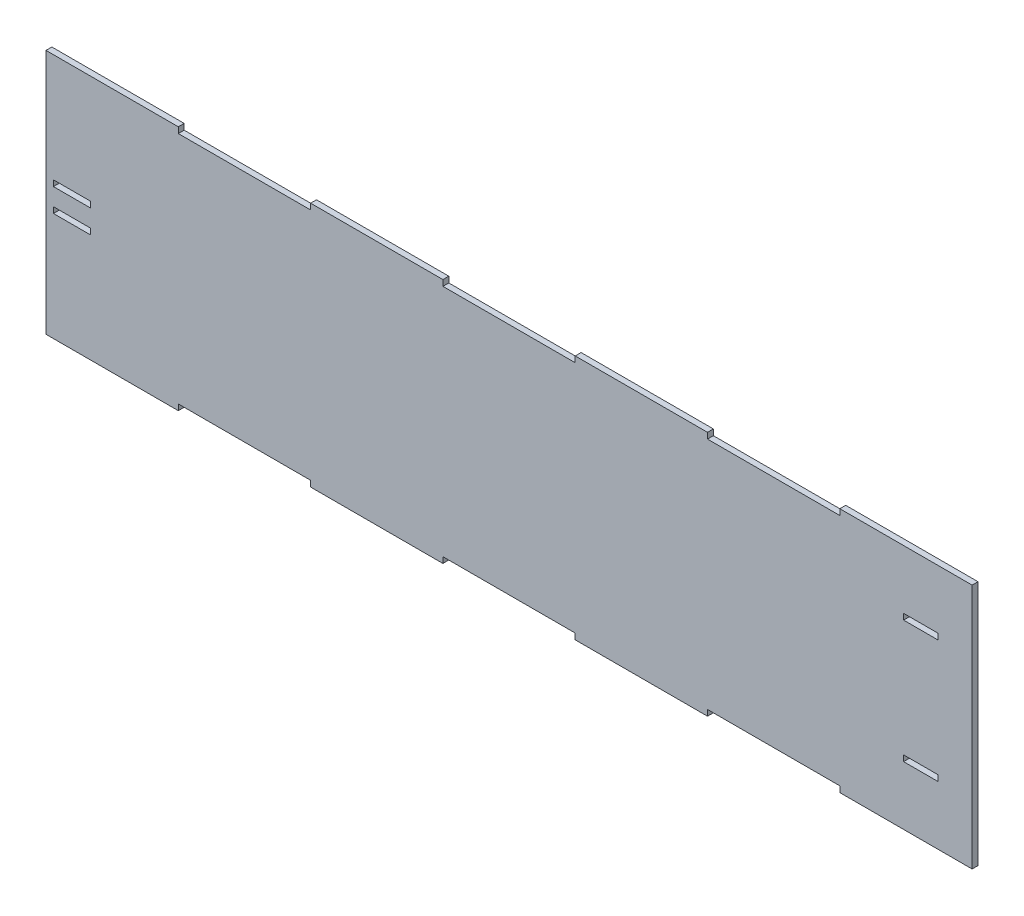
SolidWorks part; units mm, degrees
ref_plane "Front Plane" through (0, 0, 0) normal (0, 0, 1) x (1, 0, 0)
ref_plane "Top Plane" through (0, 0, 0) normal (0, 1, 0) x (1, 0, 0)
ref_plane "Right Plane" through (0, 0, 0) normal (1, 0, 0) x (0, 0, -1)
sketch "Sketch1" plane through (0, 0, 0) normal (0, 0, 1) x (1, 0, 0)
  line L0 (0, 132.75) -> (71.4286, 132.75)
  line L1 (0, 0) -> (500, 0) construction
  line L2 (0, 0) -> (0, 132.75)
  line L4 (500, 0) -> (500, 132.75)
  line L5 (71.4286, 132.75) -> (71.4286, 129.575)
  line L6 (71.4286, 129.575) -> (142.8571, 129.575)
  line L7 (142.8571, 129.575) -> (142.8571, 132.75)
  line L8 (142.8571, 132.75) -> (214.2857, 132.75)
  line L9 (214.2857, 132.75) -> (214.2857, 129.575)
  line L10 (214.2857, 129.575) -> (285.7143, 129.575)
  line L11 (285.7143, 129.575) -> (285.7143, 132.75)
  line L12 (285.7143, 132.75) -> (357.1429, 132.75)
  line L13 (357.1429, 132.75) -> (357.1429, 129.575)
  line L14 (357.1429, 129.575) -> (428.5714, 129.575)
  line L15 (428.5714, 129.575) -> (428.5714, 132.75)
  line L16 (428.5714, 132.75) -> (500, 132.75)
  line L17 (0, 66.375) -> (500, 66.375) construction
  line L18 (428.5714, 0) -> (500, 0)
  line L19 (428.5714, 3.175) -> (428.5714, 0)
  line L20 (357.1429, 3.175) -> (428.5714, 3.175)
  line L21 (357.1429, 0) -> (357.1429, 3.175)
  line L22 (285.7143, 0) -> (357.1429, 0)
  line L23 (285.7143, 3.175) -> (285.7143, 0)
  line L24 (214.2857, 3.175) -> (285.7143, 3.175)
  line L25 (214.2857, 0) -> (214.2857, 3.175)
  line L26 (142.8571, 0) -> (214.2857, 0)
  line L27 (142.8571, 3.175) -> (142.8571, 0)
  line L28 (71.4286, 3.175) -> (142.8571, 3.175)
  line L29 (71.4286, 0) -> (71.4286, 3.175)
  line L30 (0, 0) -> (71.4286, 0)
  line L31 (4, 61.675) -> (4, 66.375) construction
  line L32 (4, 61.675) -> (24, 61.675)
  line L33 (4, 61.675) -> (4, 58.5)
  line L34 (4, 58.5) -> (24, 58.5)
  line L35 (24, 61.675) -> (24, 58.5)
  line L36 (4, 71.075) -> (24, 71.075)
  line L37 (4, 71.075) -> (4, 74.25)
  line L38 (4, 74.25) -> (24, 74.25)
  line L39 (24, 71.075) -> (24, 74.25)
  line L40 (481.5, 66.375) -> (481.5, 97.875) construction
  line L41 (481.5, 34.875) -> (463, 34.875)
  line L42 (481.5, 97.875) -> (463, 97.875)
  line L43 (481.5, 97.875) -> (481.5, 101.05)
  line L44 (481.5, 101.05) -> (463, 101.05)
  line L45 (463, 97.875) -> (463, 101.05)
  line L46 (481.5, 34.875) -> (481.5, 31.7)
  line L47 (481.5, 31.7) -> (463, 31.7)
  line L48 (463, 34.875) -> (463, 31.7)
  dimension "D1" = 500
  dimension "D2" = 132.75
  dimension "D3" = 3.175
  dimension "D4" = 9.4
  dimension "D5" = 3.175
  dimension "D6" = 20
  dimension "D7" = 4.7
  dimension "D8" = 4
  dimension "D9" = 31.5
  dimension "D10" = 18.5
  dimension "D11" = 18.5
  dimension "D12" = 3.175
extrude "Boss-Extrude1" add sketch "Sketch1" along normal blind 3.175
